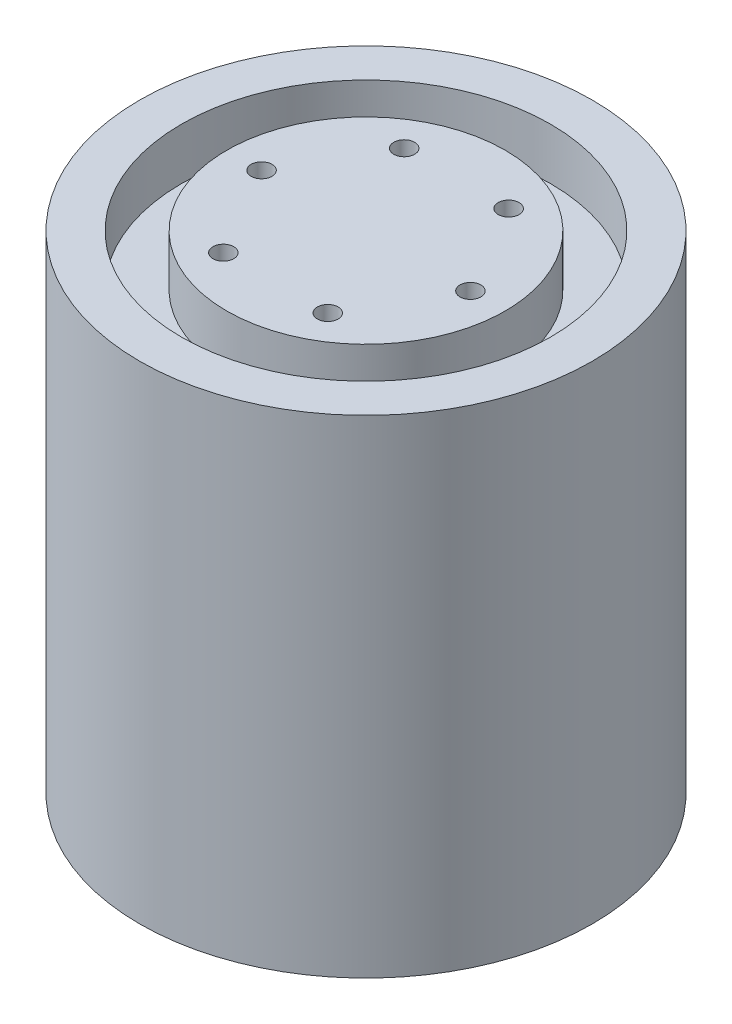
SolidWorks part; units mm, degrees
ref_plane "Alzado" through (0, 0, 0) normal (0, 0, 1) x (1, 0, 0)
ref_plane "Planta" through (0, 0, 0) normal (0, 1, 0) x (1, 0, 0)
ref_plane "Vista lateral" through (0, 0, 0) normal (1, 0, 0) x (0, 0, -1)
sketch "Croquis1" plane through (0, 0, 0) normal (0, 1, 0) x (1, 0, 0)
  circle A0 centre (0, 0) radius 32.5
  dimension "D1" = 65
extrude "Saliente-Extruir1" add sketch "Croquis1" along normal blind 70
sketch "Croquis2" plane through (0, 70, 0) normal (0, 1, 0) x (1, 0, 0)
  circle A0 centre (0, 0) radius 20
  circle A1 centre (0, 0) radius 15 construction
  circle A2 centre (15, 0) radius 1.5
  circle A3 centre (7.5, -12.9904) radius 1.5
  circle A4 centre (-7.5, -12.9904) radius 1.5
  circle A5 centre (-15, 0) radius 1.5
  circle A6 centre (-7.5, 12.9904) radius 1.5
  circle A7 centre (7.5, 12.9904) radius 1.5
  circle A8 centre (0, 0) radius 26.5
  point P19 (0, 0)
  dimension "D1" = 40
  dimension "D2" = 5
  dimension "D3" = 3
  dimension "D5" = 53
  dimension "D4" = 6
extrude "Cortar-Extruir1" cut sketch "Croquis2" against normal blind 5 contours A6 | A7 | A2 | A3 | A4 | A5
extrude "Cortar-Extruir2" cut sketch "Croquis2<3>" against normal blind 7.4 contours A8 A0 region at (-25.7505, 70, 0)
sketch "Croquis2<3>" plane through (0, 70, 0) normal (0, 1, 0) x (1, 0, 0) same geometry as "Croquis2"
